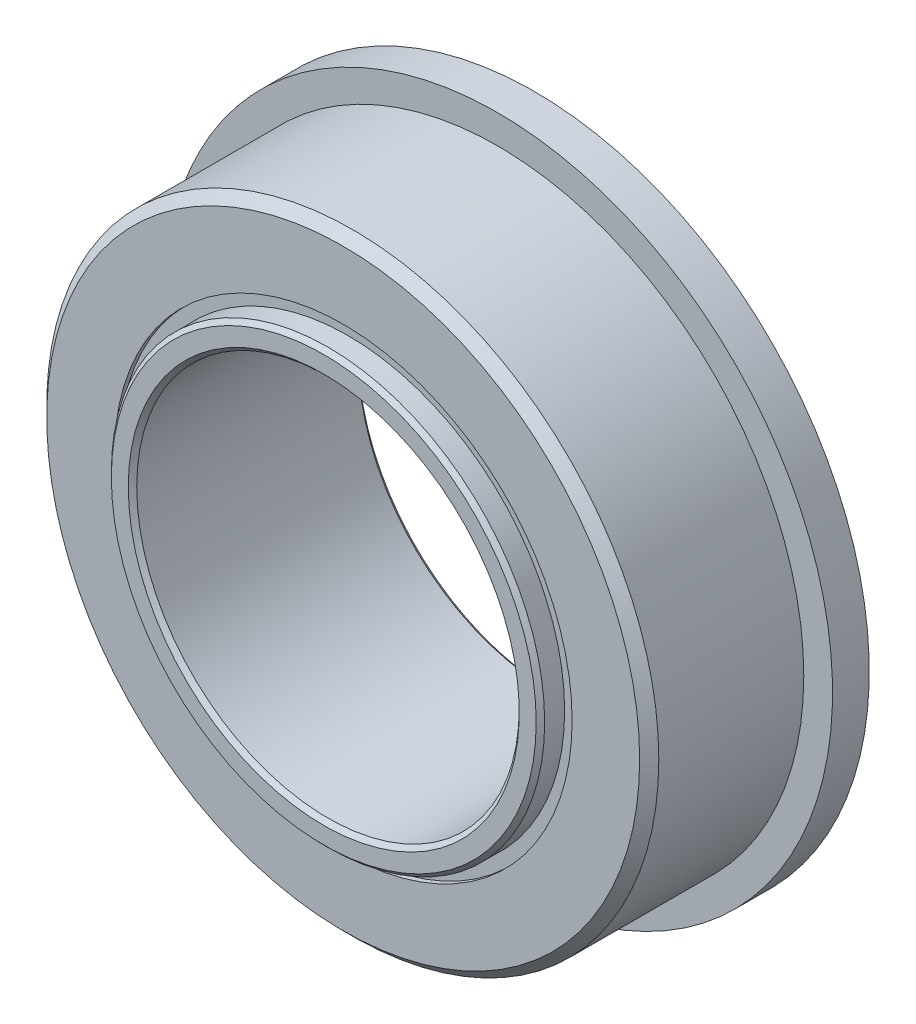
SolidWorks part; units mm, degrees
note: '?' marks a value the reader was unsure of.
ref_plane "Front Plane" through (0, 0, 0) normal (0, 0, 1) x (1, 0, 0)
ref_plane "Top Plane" through (0, 0, 0) normal (0, 1, 0) x (1, 0, 0)
ref_plane "Right Plane" through (0, 0, 0) normal (1, 0, 0) x (0, 0, -1)
sketch "Sketch1" plane through (0, 0, 0) normal (1, 0, 0) x (0, 0, -1)
  line L0 (-1.9844, 0) -> (1.9844, 0) construction
  line L1 (0, 6.35) -> (0, -6.35) construction
  line L2 (1.7859, 6.35) -> (-1.7859, 6.35)
  line L3 (-1.7859, 6.35) -> (-1.9844, 6.1516)
  line L4 (-1.9844, 6.1516) -> (-1.9844, 4.7498)
  line L5 (-1.9844, 4.7498) -> (-0.6456, 4.7498)
  line L6 (1.9844, 4.7498) -> (0.6456, 4.7498)
  line L7 (1.9844, 6.1516) -> (1.9844, 4.7498)
  line L8 (1.7859, 6.35) -> (1.9844, 6.1516)
  line L9 (0, 6.35) -> (0, 5.1594) construction
  line L10 (0, 5.1594) -> (0, 3.9688) construction
  line L11 (1.9844, 4.4958) -> (1.9844, -4.4958) construction
  line L12 (2.3876, 4.4958) -> (0.5284, 4.4958)
  line L13 (-2.3876, 4.4958) -> (-2.3876, 3.9688)
  line L14 (-2.3876, 3.9688) -> (2.3876, 3.9688)
  line L15 (2.3876, 3.9688) -> (2.3876, 4.4958)
  line L16 (-2.3876, 4.2323) -> (2.3876, 4.2323) construction
  line L17 (-0.5284, 4.4958) -> (-2.3876, 4.4958)
  circle A1 centre (0, 4.8937) radius 0.6615 construction
  arc A2 (-0.6456, 4.7498) -> (0.6456, 4.7498) centre (0, 4.8937) cw
  arc A3 (-0.5284, 4.4958) -> (0.5284, 4.4958) centre (0, 4.8937) ccw
  point P14 (0, 3.9688)
  dimension "D3" = 0.527
  dimension "D4" = 1.3229
  dimension "D1" = 45
  dimension "Width" = 3.9688
  dimension "OD" = 12.7
  dimension "D2" = 0.1984
  dimension "Shaft Dia" = 7.9375
  dimension "D5" = 0.254
  dimension "Inner Ring" = 8.9916
  dimension "Ring Width" = 4.7752
revolve "Revolve1" add sketch "Sketch1" angle 360 about L0
sketch "Sketch4" plane through (0, 0, 0) normal (1, 0, 0) x (0, 0, -1)
  line L0 (-0.6615, 4.8937) -> (0.6615, 4.8937)
  circle A0 centre (0, 4.8937) radius 0.6615 construction
  arc A2 (-0.6615, 4.8937) -> (0.6615, 4.8937) centre (0, 4.8937) cw
revolve "Revolve4" add sketch "Sketch4" angle 360 about L0
chamfer "Chamfer1" distance 0.0878 angle 45 4 edges at (4.4958, 0, 2.3876) (3.9688, 0, 2.3876) (3.9688, 0, -2.3876) (4.4958, 0, -2.3876)
ref_axis "Axis1" through (0, 0, -1.9844) along (0, 0, 1)?
pattern_circular "CirPattern1" count 12 every 30 about axis through (0, 0, 0) along (0, 0, 1) of bodies 104
sketch "Sketch5" plane through (0, 0, 0) normal (1, 0, 0) x (0, 0, -1)
  line L0 (-1.9844, 4.7498) -> (-0.6456, 4.7498) construction
  line L1 (-1.8852, 4.7498) -> (-0.6615, 4.7498)
  line L2 (-1.8852, 4.7498) -> (-1.8852, 4.4958)
  line L3 (-1.8852, 4.4958) -> (-0.6615, 4.4958)
  line L4 (-0.6615, 4.7498) -> (-0.6615, 4.4958)
  line L6 (1.9844, 4.7498) -> (0.6456, 4.7498) construction
  line L7 (1.8852, 4.7498) -> (0.6615, 4.7498)
  line L8 (1.8852, 4.7498) -> (1.8852, 4.4958)
  line L9 (1.8852, 4.4958) -> (0.6615, 4.4958)
  line L10 (0.6615, 4.7498) -> (0.6615, 4.4958)
  line L12 (-1.7859, 6.35) -> (-1.9844, 6.1516) construction
  line L13 (-0.5284, 4.4958) -> (-2.3876, 4.4958) construction
  line L14 (2.3876, 4.4958) -> (0.5284, 4.4958) construction
  point P18 (-1.8852, 6.2508)
revolve "Revolve5" add sketch "Sketch5" angle 360 about L0
sketch "Sketch6" plane through (0, 0, 0) normal (1, 0, 0) x (0, 0, -1)
  line L1 (1.9844, 4.7498) -> (1.2224, 4.7498)
  line L2 (1.9844, 4.7498) -> (1.9844, 6.9469)
  line L3 (1.9844, 6.9469) -> (1.2224, 6.9469)
  line L4 (1.2224, 4.7498) -> (1.2224, 6.9469)
  line L5 (1.9844, 0) -> (-1.9844, 0) construction
  dimension "Flange OD" = 13.8938
  dimension "Th" = 0.762
revolve "Revolve6" add sketch "Sketch6" angle 360 about L5
equation "\"D2@Sketch1\" = \"Width@Sketch1\"*.05"
equation "\"D2@CirPattern1\" = 360/\"Balls@CirPattern1\""
equation "\"D4@Sketch1\"=\"Width@Sketch1\"/3"
equation "\"D1@Chamfer1\"=\"D3@Sketch1\"/6"
